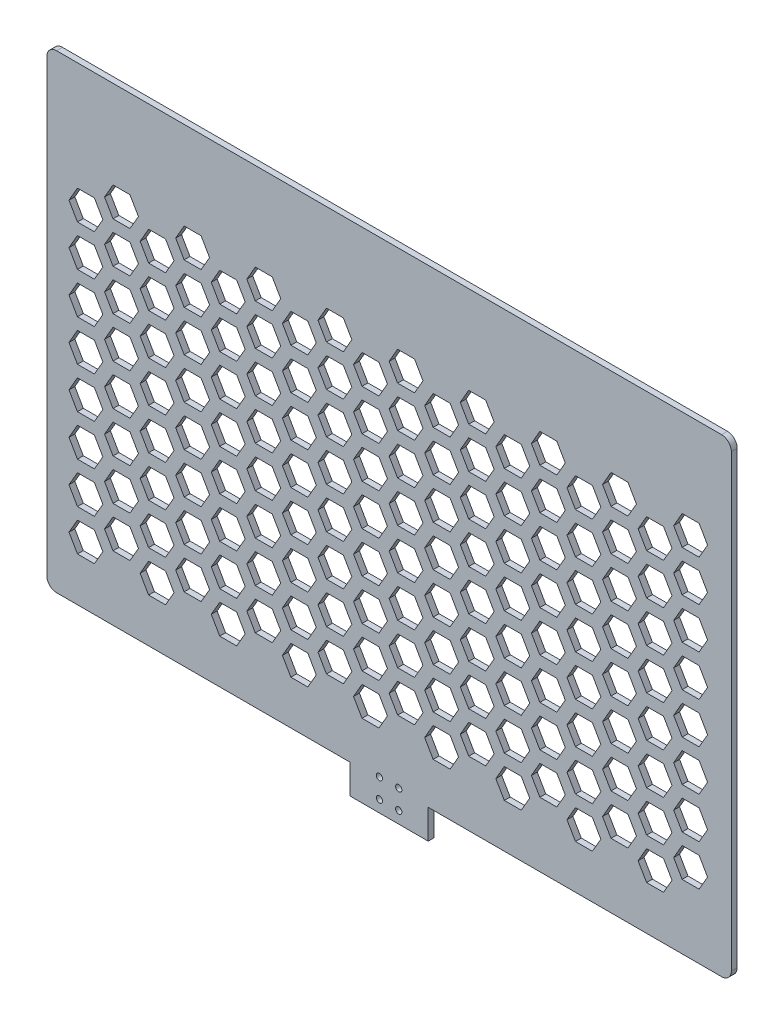
SolidWorks part; units mm, degrees
material "PMMA"
ref_plane "前视基准面" through (0, 0, 0) normal (0, 0, 1) x (1, 0, 0)
ref_plane "上视基准面" through (0, 0, 0) normal (0, 1, 0) x (1, 0, 0)
ref_plane "右视基准面" through (0, 0, 0) normal (1, 0, 0) x (0, 0, -1)
other "Configuration Table"
sketch "草图1" plane through (0, 0, 0) normal (0, 0, 1) x (1, 0, 0)
  line L1 (20, 11) -> (-20, 11)
  line L2 (20, 11) -> (20, -11)
  line L3 (20, -11) -> (-20, -11)
  line L4 (-20, 11) -> (-20, -11)
  line L5 (20, 11) -> (-20, -11) construction
  line L6 (20, -11) -> (-20, 11) construction
  point P0 (0, 0)
  dimension "D1" = 22
  dimension "D2" = 40
extrude "凸台-拉伸1" add sketch "草图1" along normal blind 3
sketch "草图2" plane through (0, 0, 0) normal (0, 0, 1) x (1, 0, 0)
  line L0 (0, 0) -> (0, 50000) construction
  line L1 (-20, -11) -> (20, -11) construction
  line L2 (170, 244) -> (-170, 244)
  line L3 (175, 239) -> (175, 9)
  line L4 (170, 4) -> (-170, 4)
  line L5 (-175, 239) -> (-175, 9)
  line L6 (175, 244) -> (-175, 4) construction
  line L7 (175, 4) -> (-175, 244) construction
  arc A0 (175, 9) -> (170, 4) centre (170, 9) cw
  arc A1 (170, 244) -> (175, 239) centre (170, 239) cw
  arc A2 (-170, 244) -> (-175, 239) centre (-170, 239) ccw
  arc A3 (-170, 4) -> (-175, 9) centre (-170, 9) cw
  point P3 (0, 124)
  dimension "D4" = 5
  dimension "D1" = 240
  dimension "D2" = 350
  dimension "D3" = 15
extrude "凸台-拉伸2" add sketch "草图2" along normal blind 3
sketch "草图4" plane through (0, 0, 0) normal (0, 0, 1) x (1, 0, 0)
  line L1 (4.9497, 4.9497) -> (-4.9497, 4.9497) construction
  line L2 (4.9497, 4.9497) -> (4.9497, -4.9497) construction
  line L3 (4.9497, -4.9497) -> (-4.9497, -4.9497) construction
  line L4 (-4.9497, 4.9497) -> (-4.9497, -4.9497) construction
  line L5 (4.9497, 4.9497) -> (-4.9497, -4.9497) construction
  line L6 (4.9497, -4.9497) -> (-4.9497, 4.9497) construction
  circle A0 centre (-4.9497, 4.9497) radius 1.6
  circle A1 centre (4.9497, 4.9497) radius 1.6
  circle A2 centre (-4.9497, -4.9497) radius 1.6
  circle A3 centre (4.9497, -4.9497) radius 1.6
  point P0 (0, 0)
  dimension "D2" = 3.2
  dimension "D1" = 14
extrude "切除-拉伸1" cut sketch "草图4" along normal through all
sketch "草图5" plane through (0, 0, 3) normal (0, 0, 1) x (1, 0, 0)
  line L0 (-170, 4) -> (-20, 4) construction
  line L1 (-150.6699, 26.5) -> (-146.3397, 34)
  line L2 (-146.3397, 34) -> (-150.6699, 41.5)
  line L3 (-150.6699, 41.5) -> (-159.3301, 41.5)
  line L4 (-159.3301, 41.5) -> (-163.6603, 34)
  line L5 (-163.6603, 34) -> (-159.3301, 26.5)
  line L6 (-159.3301, 26.5) -> (-150.6699, 26.5)
  line L7 (-175, 239) -> (-175, 9) construction
  line L8 (-155, 34) -> (-136.8135, 44.5) construction
  line L9 (-155, 34) -> (-146.3397, 34) construction
  line L10 (-114.2959, 26.5) -> (-109.9657, 34)
  line L11 (-132.4833, 37) -> (-128.1532, 44.5)
  line L12 (-128.1532, 44.5) -> (-132.4833, 52)
  line L13 (-132.4833, 52) -> (-141.1436, 52)
  line L14 (-141.1436, 52) -> (-145.4737, 44.5)
  line L15 (-145.4737, 44.5) -> (-141.1436, 37)
  line L16 (-141.1436, 37) -> (-132.4833, 37)
  line L17 (-109.9657, 34) -> (-114.2959, 41.5)
  line L18 (-114.2959, 41.5) -> (-122.9561, 41.5)
  line L19 (-122.9561, 41.5) -> (-127.2863, 34)
  line L20 (-127.2863, 34) -> (-122.9561, 26.5)
  line L21 (-122.9561, 26.5) -> (-114.2959, 26.5)
  line L22 (-96.1093, 37) -> (-91.7792, 44.5)
  line L23 (-91.7792, 44.5) -> (-96.1093, 52)
  line L24 (-96.1093, 52) -> (-104.7696, 52)
  line L25 (-104.7696, 52) -> (-109.0997, 44.5)
  line L26 (-109.0997, 44.5) -> (-104.7696, 37)
  line L27 (-104.7696, 37) -> (-96.1093, 37)
  line L28 (-77.9219, 26.5) -> (-73.5917, 34)
  line L29 (-73.5917, 34) -> (-77.9219, 41.5)
  line L30 (-77.9219, 41.5) -> (-86.5821, 41.5)
  line L31 (-86.5821, 41.5) -> (-90.9123, 34)
  line L32 (-90.9123, 34) -> (-86.5821, 26.5)
  line L33 (-86.5821, 26.5) -> (-77.9219, 26.5)
  line L34 (-59.7353, 37) -> (-55.4052, 44.5)
  line L35 (-55.4052, 44.5) -> (-59.7353, 52)
  line L36 (-59.7353, 52) -> (-68.3956, 52)
  line L37 (-68.3956, 52) -> (-72.7257, 44.5)
  line L38 (-72.7257, 44.5) -> (-68.3956, 37)
  line L39 (-68.3956, 37) -> (-59.7353, 37)
  line L40 (-41.5479, 26.5) -> (-37.2177, 34)
  line L41 (-37.2177, 34) -> (-41.5479, 41.5)
  line L42 (-41.5479, 41.5) -> (-50.2081, 41.5)
  line L43 (-50.2081, 41.5) -> (-54.5383, 34)
  line L44 (-54.5383, 34) -> (-50.2081, 26.5)
  line L45 (-50.2081, 26.5) -> (-41.5479, 26.5)
  line L46 (-23.3613, 37) -> (-19.0312, 44.5)
  line L47 (-19.0312, 44.5) -> (-23.3613, 52)
  line L48 (-23.3613, 52) -> (-32.0216, 52)
  line L49 (-32.0216, 52) -> (-36.3517, 44.5)
  line L50 (-36.3517, 44.5) -> (-32.0216, 37)
  line L51 (-32.0216, 37) -> (-23.3613, 37)
  line L52 (-5.1739, 26.5) -> (-0.8437, 34)
  line L53 (-0.8437, 34) -> (-5.1739, 41.5)
  line L54 (-5.1739, 41.5) -> (-13.8341, 41.5)
  line L55 (-13.8341, 41.5) -> (-18.1643, 34)
  line L56 (-18.1643, 34) -> (-13.8341, 26.5)
  line L57 (-13.8341, 26.5) -> (-5.1739, 26.5)
  line L58 (13.0127, 37) -> (17.3428, 44.5)
  line L59 (17.3428, 44.5) -> (13.0127, 52)
  line L60 (13.0127, 52) -> (4.3524, 52)
  line L61 (4.3524, 52) -> (0.0223, 44.5)
  line L62 (0.0223, 44.5) -> (4.3524, 37)
  line L63 (4.3524, 37) -> (13.0127, 37)
  line L64 (31.2001, 26.5) -> (35.5303, 34)
  line L65 (35.5303, 34) -> (31.2001, 41.5)
  line L66 (31.2001, 41.5) -> (22.5399, 41.5)
  line L67 (22.5399, 41.5) -> (18.2097, 34)
  line L68 (18.2097, 34) -> (22.5399, 26.5)
  line L69 (22.5399, 26.5) -> (31.2001, 26.5)
  line L70 (49.3867, 37) -> (53.7168, 44.5)
  line L71 (53.7168, 44.5) -> (49.3867, 52)
  line L72 (49.3867, 52) -> (40.7264, 52)
  line L73 (40.7264, 52) -> (36.3963, 44.5)
  line L74 (36.3963, 44.5) -> (40.7264, 37)
  line L75 (40.7264, 37) -> (49.3867, 37)
  line L76 (67.5741, 26.5) -> (71.9043, 34)
  line L77 (71.9043, 34) -> (67.5741, 41.5)
  line L78 (67.5741, 41.5) -> (58.9139, 41.5)
  line L79 (58.9139, 41.5) -> (54.5837, 34)
  line L80 (54.5837, 34) -> (58.9139, 26.5)
  line L81 (58.9139, 26.5) -> (67.5741, 26.5)
  line L82 (85.7607, 37) -> (90.0908, 44.5)
  line L83 (90.0908, 44.5) -> (85.7607, 52)
  line L84 (85.7607, 52) -> (77.1004, 52)
  line L85 (77.1004, 52) -> (72.7703, 44.5)
  line L86 (72.7703, 44.5) -> (77.1004, 37)
  line L87 (77.1004, 37) -> (85.7607, 37)
  line L88 (103.9481, 26.5) -> (108.2783, 34)
  line L89 (108.2783, 34) -> (103.9481, 41.5)
  line L90 (103.9481, 41.5) -> (95.2879, 41.5)
  line L91 (95.2879, 41.5) -> (90.9577, 34)
  line L92 (90.9577, 34) -> (95.2879, 26.5)
  line L93 (95.2879, 26.5) -> (103.9481, 26.5)
  line L94 (122.1347, 37) -> (126.4648, 44.5)
  line L95 (126.4648, 44.5) -> (122.1347, 52)
  line L96 (122.1347, 52) -> (113.4744, 52)
  line L97 (113.4744, 52) -> (109.1443, 44.5)
  line L98 (109.1443, 44.5) -> (113.4744, 37)
  line L99 (113.4744, 37) -> (122.1347, 37)
  line L100 (140.3221, 26.5) -> (144.6523, 34)
  line L101 (144.6523, 34) -> (140.3221, 41.5)
  line L102 (140.3221, 41.5) -> (131.6619, 41.5)
  line L103 (131.6619, 41.5) -> (127.3317, 34)
  line L104 (127.3317, 34) -> (131.6619, 26.5)
  line L105 (131.6619, 26.5) -> (140.3221, 26.5)
  line L106 (158.5087, 37) -> (162.8388, 44.5)
  line L107 (162.8388, 44.5) -> (158.5087, 52)
  line L108 (158.5087, 52) -> (149.8484, 52)
  line L109 (149.8484, 52) -> (145.5183, 44.5)
  line L110 (145.5183, 44.5) -> (149.8484, 37)
  line L111 (149.8484, 37) -> (158.5087, 37)
  line L112 (20, -11) -> (20, 4) construction
  line L113 (-20, -11) -> (20, -11) construction
  line L114 (-150.6699, 47.5) -> (-146.3397, 55)
  line L115 (-146.3397, 55) -> (-150.6699, 62.5)
  line L116 (-150.6699, 62.5) -> (-159.3301, 62.5)
  line L117 (-159.3301, 62.5) -> (-163.6603, 55)
  line L118 (-163.6603, 55) -> (-159.3301, 47.5)
  line L119 (-159.3301, 47.5) -> (-150.6699, 47.5)
  line L120 (-114.2959, 47.5) -> (-109.9657, 55)
  line L121 (-132.4833, 58) -> (-128.1532, 65.5)
  line L122 (-128.1532, 65.5) -> (-132.4833, 73)
  line L123 (-132.4833, 73) -> (-141.1436, 73)
  line L124 (-141.1436, 73) -> (-145.4737, 65.5)
  line L125 (-145.4737, 65.5) -> (-141.1436, 58)
  line L126 (-141.1436, 58) -> (-132.4833, 58)
  line L127 (-109.9657, 55) -> (-114.2959, 62.5)
  line L128 (-114.2959, 62.5) -> (-122.9561, 62.5)
  line L129 (-122.9561, 62.5) -> (-127.2863, 55)
  line L130 (-127.2863, 55) -> (-122.9561, 47.5)
  line L131 (-122.9561, 47.5) -> (-114.2959, 47.5)
  line L132 (-96.1093, 58) -> (-91.7792, 65.5)
  line L133 (-91.7792, 65.5) -> (-96.1093, 73)
  line L134 (-96.1093, 73) -> (-104.7696, 73)
  line L135 (-104.7696, 73) -> (-109.0997, 65.5)
  line L136 (-109.0997, 65.5) -> (-104.7696, 58)
  line L137 (-104.7696, 58) -> (-96.1093, 58)
  line L138 (-77.9219, 47.5) -> (-73.5917, 55)
  line L139 (-73.5917, 55) -> (-77.9219, 62.5)
  line L140 (-77.9219, 62.5) -> (-86.5821, 62.5)
  line L141 (-86.5821, 62.5) -> (-90.9123, 55)
  line L142 (-90.9123, 55) -> (-86.5821, 47.5)
  line L143 (-86.5821, 47.5) -> (-77.9219, 47.5)
  line L144 (-59.7353, 58) -> (-55.4052, 65.5)
  line L145 (-55.4052, 65.5) -> (-59.7353, 73)
  line L146 (-59.7353, 73) -> (-68.3956, 73)
  line L147 (-68.3956, 73) -> (-72.7257, 65.5)
  line L148 (-72.7257, 65.5) -> (-68.3956, 58)
  line L149 (-68.3956, 58) -> (-59.7353, 58)
  line L150 (-41.5479, 47.5) -> (-37.2177, 55)
  line L151 (-37.2177, 55) -> (-41.5479, 62.5)
  line L152 (-41.5479, 62.5) -> (-50.2081, 62.5)
  line L153 (-50.2081, 62.5) -> (-54.5383, 55)
  line L154 (-54.5383, 55) -> (-50.2081, 47.5)
  line L155 (-50.2081, 47.5) -> (-41.5479, 47.5)
  line L156 (-23.3613, 58) -> (-19.0312, 65.5)
  line L157 (-19.0312, 65.5) -> (-23.3613, 73)
  line L158 (-23.3613, 73) -> (-32.0216, 73)
  line L159 (-32.0216, 73) -> (-36.3517, 65.5)
  line L160 (-36.3517, 65.5) -> (-32.0216, 58)
  line L161 (-32.0216, 58) -> (-23.3613, 58)
  line L162 (-5.1739, 47.5) -> (-0.8437, 55)
  line L163 (-0.8437, 55) -> (-5.1739, 62.5)
  line L164 (-5.1739, 62.5) -> (-13.8341, 62.5)
  line L165 (-13.8341, 62.5) -> (-18.1643, 55)
  line L166 (-18.1643, 55) -> (-13.8341, 47.5)
  line L167 (-13.8341, 47.5) -> (-5.1739, 47.5)
  line L168 (13.0127, 58) -> (17.3428, 65.5)
  line L169 (17.3428, 65.5) -> (13.0127, 73)
  line L170 (13.0127, 73) -> (4.3524, 73)
  line L171 (4.3524, 73) -> (0.0223, 65.5)
  line L172 (0.0223, 65.5) -> (4.3524, 58)
  line L173 (4.3524, 58) -> (13.0127, 58)
  line L174 (31.2001, 47.5) -> (35.5303, 55)
  line L175 (35.5303, 55) -> (31.2001, 62.5)
  line L176 (31.2001, 62.5) -> (22.5399, 62.5)
  line L177 (22.5399, 62.5) -> (18.2097, 55)
  line L178 (18.2097, 55) -> (22.5399, 47.5)
  line L179 (22.5399, 47.5) -> (31.2001, 47.5)
  line L180 (49.3867, 58) -> (53.7168, 65.5)
  line L181 (53.7168, 65.5) -> (49.3867, 73)
  line L182 (49.3867, 73) -> (40.7264, 73)
  line L183 (40.7264, 73) -> (36.3963, 65.5)
  line L184 (36.3963, 65.5) -> (40.7264, 58)
  line L185 (40.7264, 58) -> (49.3867, 58)
  line L186 (67.5741, 47.5) -> (71.9043, 55)
  line L187 (71.9043, 55) -> (67.5741, 62.5)
  line L188 (67.5741, 62.5) -> (58.9139, 62.5)
  line L189 (58.9139, 62.5) -> (54.5837, 55)
  line L190 (54.5837, 55) -> (58.9139, 47.5)
  line L191 (58.9139, 47.5) -> (67.5741, 47.5)
  line L192 (85.7607, 58) -> (90.0908, 65.5)
  line L193 (90.0908, 65.5) -> (85.7607, 73)
  line L194 (85.7607, 73) -> (77.1004, 73)
  line L195 (77.1004, 73) -> (72.7703, 65.5)
  line L196 (72.7703, 65.5) -> (77.1004, 58)
  line L197 (77.1004, 58) -> (85.7607, 58)
  line L198 (103.9481, 47.5) -> (108.2783, 55)
  line L199 (108.2783, 55) -> (103.9481, 62.5)
  line L200 (103.9481, 62.5) -> (95.2879, 62.5)
  line L201 (95.2879, 62.5) -> (90.9577, 55)
  line L202 (90.9577, 55) -> (95.2879, 47.5)
  line L203 (95.2879, 47.5) -> (103.9481, 47.5)
  line L204 (122.1347, 58) -> (126.4648, 65.5)
  line L205 (126.4648, 65.5) -> (122.1347, 73)
  line L206 (122.1347, 73) -> (113.4744, 73)
  line L207 (113.4744, 73) -> (109.1443, 65.5)
  line L208 (109.1443, 65.5) -> (113.4744, 58)
  line L209 (113.4744, 58) -> (122.1347, 58)
  line L210 (140.3221, 47.5) -> (144.6523, 55)
  line L211 (144.6523, 55) -> (140.3221, 62.5)
  line L212 (140.3221, 62.5) -> (131.6619, 62.5)
  line L213 (131.6619, 62.5) -> (127.3317, 55)
  line L214 (127.3317, 55) -> (131.6619, 47.5)
  line L215 (131.6619, 47.5) -> (140.3221, 47.5)
  line L216 (158.5087, 58) -> (162.8388, 65.5)
  line L217 (162.8388, 65.5) -> (158.5087, 73)
  line L218 (158.5087, 73) -> (149.8484, 73)
  line L219 (149.8484, 73) -> (145.5183, 65.5)
  line L220 (145.5183, 65.5) -> (149.8484, 58)
  line L221 (149.8484, 58) -> (158.5087, 58)
  line L222 (-155, 55) -> (-136.8135, 65.5) construction
  line L223 (-155, 55) -> (-146.3397, 55) construction
  line L224 (-150.6699, 68.5) -> (-146.3397, 76)
  line L225 (-146.3397, 76) -> (-150.6699, 83.5)
  line L226 (-150.6699, 83.5) -> (-159.3301, 83.5)
  line L227 (-159.3301, 83.5) -> (-163.6603, 76)
  line L228 (-163.6603, 76) -> (-159.3301, 68.5)
  line L229 (-159.3301, 68.5) -> (-150.6699, 68.5)
  line L230 (-114.2959, 68.5) -> (-109.9657, 76)
  line L231 (-132.4833, 79) -> (-128.1532, 86.5)
  line L232 (-128.1532, 86.5) -> (-132.4833, 94)
  line L233 (-132.4833, 94) -> (-141.1436, 94)
  line L234 (-141.1436, 94) -> (-145.4737, 86.5)
  line L235 (-145.4737, 86.5) -> (-141.1436, 79)
  line L236 (-141.1436, 79) -> (-132.4833, 79)
  line L237 (-109.9657, 76) -> (-114.2959, 83.5)
  line L238 (-114.2959, 83.5) -> (-122.9561, 83.5)
  line L239 (-122.9561, 83.5) -> (-127.2863, 76)
  line L240 (-127.2863, 76) -> (-122.9561, 68.5)
  line L241 (-122.9561, 68.5) -> (-114.2959, 68.5)
  line L242 (-96.1093, 79) -> (-91.7792, 86.5)
  line L243 (-91.7792, 86.5) -> (-96.1093, 94)
  line L244 (-96.1093, 94) -> (-104.7696, 94)
  line L245 (-104.7696, 94) -> (-109.0997, 86.5)
  line L246 (-109.0997, 86.5) -> (-104.7696, 79)
  line L247 (-104.7696, 79) -> (-96.1093, 79)
  line L248 (-77.9219, 68.5) -> (-73.5917, 76)
  line L249 (-73.5917, 76) -> (-77.9219, 83.5)
  line L250 (-77.9219, 83.5) -> (-86.5821, 83.5)
  line L251 (-86.5821, 83.5) -> (-90.9123, 76)
  line L252 (-90.9123, 76) -> (-86.5821, 68.5)
  line L253 (-86.5821, 68.5) -> (-77.9219, 68.5)
  line L254 (-59.7353, 79) -> (-55.4052, 86.5)
  line L255 (-55.4052, 86.5) -> (-59.7353, 94)
  line L256 (-59.7353, 94) -> (-68.3956, 94)
  line L257 (-68.3956, 94) -> (-72.7257, 86.5)
  line L258 (-72.7257, 86.5) -> (-68.3956, 79)
  line L259 (-68.3956, 79) -> (-59.7353, 79)
  line L260 (-41.5479, 68.5) -> (-37.2177, 76)
  line L261 (-37.2177, 76) -> (-41.5479, 83.5)
  line L262 (-41.5479, 83.5) -> (-50.2081, 83.5)
  line L263 (-50.2081, 83.5) -> (-54.5383, 76)
  line L264 (-54.5383, 76) -> (-50.2081, 68.5)
  line L265 (-50.2081, 68.5) -> (-41.5479, 68.5)
  line L266 (-23.3613, 79) -> (-19.0312, 86.5)
  line L267 (-19.0312, 86.5) -> (-23.3613, 94)
  line L268 (-23.3613, 94) -> (-32.0216, 94)
  line L269 (-32.0216, 94) -> (-36.3517, 86.5)
  line L270 (-36.3517, 86.5) -> (-32.0216, 79)
  line L271 (-32.0216, 79) -> (-23.3613, 79)
  line L272 (-5.1739, 68.5) -> (-0.8437, 76)
  line L273 (-0.8437, 76) -> (-5.1739, 83.5)
  line L274 (-5.1739, 83.5) -> (-13.8341, 83.5)
  line L275 (-13.8341, 83.5) -> (-18.1643, 76)
  line L276 (-18.1643, 76) -> (-13.8341, 68.5)
  line L277 (-13.8341, 68.5) -> (-5.1739, 68.5)
  line L278 (13.0127, 79) -> (17.3428, 86.5)
  line L279 (17.3428, 86.5) -> (13.0127, 94)
  line L280 (13.0127, 94) -> (4.3524, 94)
  line L281 (4.3524, 94) -> (0.0223, 86.5)
  line L282 (0.0223, 86.5) -> (4.3524, 79)
  line L283 (4.3524, 79) -> (13.0127, 79)
  line L284 (31.2001, 68.5) -> (35.5303, 76)
  line L285 (35.5303, 76) -> (31.2001, 83.5)
  line L286 (31.2001, 83.5) -> (22.5399, 83.5)
  line L287 (22.5399, 83.5) -> (18.2097, 76)
  line L288 (18.2097, 76) -> (22.5399, 68.5)
  line L289 (22.5399, 68.5) -> (31.2001, 68.5)
  line L290 (49.3867, 79) -> (53.7168, 86.5)
  line L291 (53.7168, 86.5) -> (49.3867, 94)
  line L292 (49.3867, 94) -> (40.7264, 94)
  line L293 (40.7264, 94) -> (36.3963, 86.5)
  line L294 (36.3963, 86.5) -> (40.7264, 79)
  line L295 (40.7264, 79) -> (49.3867, 79)
  line L296 (67.5741, 68.5) -> (71.9043, 76)
  line L297 (71.9043, 76) -> (67.5741, 83.5)
  line L298 (67.5741, 83.5) -> (58.9139, 83.5)
  line L299 (58.9139, 83.5) -> (54.5837, 76)
  line L300 (54.5837, 76) -> (58.9139, 68.5)
  line L301 (58.9139, 68.5) -> (67.5741, 68.5)
  line L302 (85.7607, 79) -> (90.0908, 86.5)
  line L303 (90.0908, 86.5) -> (85.7607, 94)
  line L304 (85.7607, 94) -> (77.1004, 94)
  line L305 (77.1004, 94) -> (72.7703, 86.5)
  line L306 (72.7703, 86.5) -> (77.1004, 79)
  line L307 (77.1004, 79) -> (85.7607, 79)
  line L308 (103.9481, 68.5) -> (108.2783, 76)
  line L309 (108.2783, 76) -> (103.9481, 83.5)
  line L310 (103.9481, 83.5) -> (95.2879, 83.5)
  line L311 (95.2879, 83.5) -> (90.9577, 76)
  line L312 (90.9577, 76) -> (95.2879, 68.5)
  line L313 (95.2879, 68.5) -> (103.9481, 68.5)
  line L314 (122.1347, 79) -> (126.4648, 86.5)
  line L315 (126.4648, 86.5) -> (122.1347, 94)
  line L316 (122.1347, 94) -> (113.4744, 94)
  line L317 (113.4744, 94) -> (109.1443, 86.5)
  line L318 (109.1443, 86.5) -> (113.4744, 79)
  line L319 (113.4744, 79) -> (122.1347, 79)
  line L320 (140.3221, 68.5) -> (144.6523, 76)
  line L321 (144.6523, 76) -> (140.3221, 83.5)
  line L322 (140.3221, 83.5) -> (131.6619, 83.5)
  line L323 (131.6619, 83.5) -> (127.3317, 76)
  line L324 (127.3317, 76) -> (131.6619, 68.5)
  line L325 (131.6619, 68.5) -> (140.3221, 68.5)
  line L326 (158.5087, 79) -> (162.8388, 86.5)
  line L327 (162.8388, 86.5) -> (158.5087, 94)
  line L328 (158.5087, 94) -> (149.8484, 94)
  line L329 (149.8484, 94) -> (145.5183, 86.5)
  line L330 (145.5183, 86.5) -> (149.8484, 79)
  line L331 (149.8484, 79) -> (158.5087, 79)
  line L332 (-155, 76) -> (-136.8135, 86.5) construction
  line L333 (-155, 76) -> (-146.3397, 76) construction
  line L334 (-150.6699, 89.5) -> (-146.3397, 97)
  line L335 (-146.3397, 97) -> (-150.6699, 104.5)
  line L336 (-150.6699, 104.5) -> (-159.3301, 104.5)
  line L337 (-159.3301, 104.5) -> (-163.6603, 97)
  line L338 (-163.6603, 97) -> (-159.3301, 89.5)
  line L339 (-159.3301, 89.5) -> (-150.6699, 89.5)
  line L340 (-114.2959, 89.5) -> (-109.9657, 97)
  line L341 (-132.4833, 100) -> (-128.1532, 107.5)
  line L342 (-128.1532, 107.5) -> (-132.4833, 115)
  line L343 (-132.4833, 115) -> (-141.1436, 115)
  line L344 (-141.1436, 115) -> (-145.4737, 107.5)
  line L345 (-145.4737, 107.5) -> (-141.1436, 100)
  line L346 (-141.1436, 100) -> (-132.4833, 100)
  line L347 (-109.9657, 97) -> (-114.2959, 104.5)
  line L348 (-114.2959, 104.5) -> (-122.9561, 104.5)
  line L349 (-122.9561, 104.5) -> (-127.2863, 97)
  line L350 (-127.2863, 97) -> (-122.9561, 89.5)
  line L351 (-122.9561, 89.5) -> (-114.2959, 89.5)
  line L352 (-96.1093, 100) -> (-91.7792, 107.5)
  line L353 (-91.7792, 107.5) -> (-96.1093, 115)
  line L354 (-96.1093, 115) -> (-104.7696, 115)
  line L355 (-104.7696, 115) -> (-109.0997, 107.5)
  line L356 (-109.0997, 107.5) -> (-104.7696, 100)
  line L357 (-104.7696, 100) -> (-96.1093, 100)
  line L358 (-77.9219, 89.5) -> (-73.5917, 97)
  line L359 (-73.5917, 97) -> (-77.9219, 104.5)
  line L360 (-77.9219, 104.5) -> (-86.5821, 104.5)
  line L361 (-86.5821, 104.5) -> (-90.9123, 97)
  line L362 (-90.9123, 97) -> (-86.5821, 89.5)
  line L363 (-86.5821, 89.5) -> (-77.9219, 89.5)
  line L364 (-59.7353, 100) -> (-55.4052, 107.5)
  line L365 (-55.4052, 107.5) -> (-59.7353, 115)
  line L366 (-59.7353, 115) -> (-68.3956, 115)
  line L367 (-68.3956, 115) -> (-72.7257, 107.5)
  line L368 (-72.7257, 107.5) -> (-68.3956, 100)
  line L369 (-68.3956, 100) -> (-59.7353, 100)
  line L370 (-41.5479, 89.5) -> (-37.2177, 97)
  line L371 (-37.2177, 97) -> (-41.5479, 104.5)
  line L372 (-41.5479, 104.5) -> (-50.2081, 104.5)
  line L373 (-50.2081, 104.5) -> (-54.5383, 97)
  line L374 (-54.5383, 97) -> (-50.2081, 89.5)
  line L375 (-50.2081, 89.5) -> (-41.5479, 89.5)
  line L376 (-23.3613, 100) -> (-19.0312, 107.5)
  line L377 (-19.0312, 107.5) -> (-23.3613, 115)
  line L378 (-23.3613, 115) -> (-32.0216, 115)
  line L379 (-32.0216, 115) -> (-36.3517, 107.5)
  line L380 (-36.3517, 107.5) -> (-32.0216, 100)
  line L381 (-32.0216, 100) -> (-23.3613, 100)
  line L382 (-5.1739, 89.5) -> (-0.8437, 97)
  line L383 (-0.8437, 97) -> (-5.1739, 104.5)
  line L384 (-5.1739, 104.5) -> (-13.8341, 104.5)
  line L385 (-13.8341, 104.5) -> (-18.1643, 97)
  line L386 (-18.1643, 97) -> (-13.8341, 89.5)
  line L387 (-13.8341, 89.5) -> (-5.1739, 89.5)
  line L388 (13.0127, 100) -> (17.3428, 107.5)
  line L389 (17.3428, 107.5) -> (13.0127, 115)
  line L390 (13.0127, 115) -> (4.3524, 115)
  line L391 (4.3524, 115) -> (0.0223, 107.5)
  line L392 (0.0223, 107.5) -> (4.3524, 100)
  line L393 (4.3524, 100) -> (13.0127, 100)
  line L394 (31.2001, 89.5) -> (35.5303, 97)
  line L395 (35.5303, 97) -> (31.2001, 104.5)
  line L396 (31.2001, 104.5) -> (22.5399, 104.5)
  line L397 (22.5399, 104.5) -> (18.2097, 97)
  line L398 (18.2097, 97) -> (22.5399, 89.5)
  line L399 (22.5399, 89.5) -> (31.2001, 89.5)
  line L400 (49.3867, 100) -> (53.7168, 107.5)
  line L401 (53.7168, 107.5) -> (49.3867, 115)
  line L402 (49.3867, 115) -> (40.7264, 115)
  line L403 (40.7264, 115) -> (36.3963, 107.5)
  line L404 (36.3963, 107.5) -> (40.7264, 100)
  line L405 (40.7264, 100) -> (49.3867, 100)
  line L406 (67.5741, 89.5) -> (71.9043, 97)
  line L407 (71.9043, 97) -> (67.5741, 104.5)
  line L408 (67.5741, 104.5) -> (58.9139, 104.5)
  line L409 (58.9139, 104.5) -> (54.5837, 97)
  line L410 (54.5837, 97) -> (58.9139, 89.5)
  line L411 (58.9139, 89.5) -> (67.5741, 89.5)
  line L412 (85.7607, 100) -> (90.0908, 107.5)
  line L413 (90.0908, 107.5) -> (85.7607, 115)
  line L414 (85.7607, 115) -> (77.1004, 115)
  line L415 (77.1004, 115) -> (72.7703, 107.5)
  line L416 (72.7703, 107.5) -> (77.1004, 100)
  line L417 (77.1004, 100) -> (85.7607, 100)
  line L418 (103.9481, 89.5) -> (108.2783, 97)
  line L419 (108.2783, 97) -> (103.9481, 104.5)
  line L420 (103.9481, 104.5) -> (95.2879, 104.5)
  line L421 (95.2879, 104.5) -> (90.9577, 97)
  line L422 (90.9577, 97) -> (95.2879, 89.5)
  line L423 (95.2879, 89.5) -> (103.9481, 89.5)
  line L424 (122.1347, 100) -> (126.4648, 107.5)
  line L425 (126.4648, 107.5) -> (122.1347, 115)
  line L426 (122.1347, 115) -> (113.4744, 115)
  line L427 (113.4744, 115) -> (109.1443, 107.5)
  line L428 (109.1443, 107.5) -> (113.4744, 100)
  line L429 (113.4744, 100) -> (122.1347, 100)
  line L430 (140.3221, 89.5) -> (144.6523, 97)
  line L431 (144.6523, 97) -> (140.3221, 104.5)
  line L432 (140.3221, 104.5) -> (131.6619, 104.5)
  line L433 (131.6619, 104.5) -> (127.3317, 97)
  line L434 (127.3317, 97) -> (131.6619, 89.5)
  line L435 (131.6619, 89.5) -> (140.3221, 89.5)
  line L436 (158.5087, 100) -> (162.8388, 107.5)
  line L437 (162.8388, 107.5) -> (158.5087, 115)
  line L438 (158.5087, 115) -> (149.8484, 115)
  line L439 (149.8484, 115) -> (145.5183, 107.5)
  line L440 (145.5183, 107.5) -> (149.8484, 100)
  line L441 (149.8484, 100) -> (158.5087, 100)
  line L442 (-155, 97) -> (-136.8135, 107.5) construction
  line L443 (-155, 97) -> (-146.3397, 97) construction
  line L444 (-150.6699, 110.5) -> (-146.3397, 118)
  line L445 (-146.3397, 118) -> (-150.6699, 125.5)
  line L446 (-150.6699, 125.5) -> (-159.3301, 125.5)
  line L447 (-159.3301, 125.5) -> (-163.6603, 118)
  line L448 (-163.6603, 118) -> (-159.3301, 110.5)
  line L449 (-159.3301, 110.5) -> (-150.6699, 110.5)
  line L450 (-114.2959, 110.5) -> (-109.9657, 118)
  line L451 (-132.4833, 121) -> (-128.1532, 128.5)
  line L452 (-128.1532, 128.5) -> (-132.4833, 136)
  line L453 (-132.4833, 136) -> (-141.1436, 136)
  line L454 (-141.1436, 136) -> (-145.4737, 128.5)
  line L455 (-145.4737, 128.5) -> (-141.1436, 121)
  line L456 (-141.1436, 121) -> (-132.4833, 121)
  line L457 (-109.9657, 118) -> (-114.2959, 125.5)
  line L458 (-114.2959, 125.5) -> (-122.9561, 125.5)
  line L459 (-122.9561, 125.5) -> (-127.2863, 118)
  line L460 (-127.2863, 118) -> (-122.9561, 110.5)
  line L461 (-122.9561, 110.5) -> (-114.2959, 110.5)
  line L462 (-96.1093, 121) -> (-91.7792, 128.5)
  line L463 (-91.7792, 128.5) -> (-96.1093, 136)
  line L464 (-96.1093, 136) -> (-104.7696, 136)
  line L465 (-104.7696, 136) -> (-109.0997, 128.5)
  line L466 (-109.0997, 128.5) -> (-104.7696, 121)
  line L467 (-104.7696, 121) -> (-96.1093, 121)
  line L468 (-77.9219, 110.5) -> (-73.5917, 118)
  line L469 (-73.5917, 118) -> (-77.9219, 125.5)
  line L470 (-77.9219, 125.5) -> (-86.5821, 125.5)
  line L471 (-86.5821, 125.5) -> (-90.9123, 118)
  line L472 (-90.9123, 118) -> (-86.5821, 110.5)
  line L473 (-86.5821, 110.5) -> (-77.9219, 110.5)
  line L474 (-59.7353, 121) -> (-55.4052, 128.5)
  line L475 (-55.4052, 128.5) -> (-59.7353, 136)
  line L476 (-59.7353, 136) -> (-68.3956, 136)
  line L477 (-68.3956, 136) -> (-72.7257, 128.5)
  line L478 (-72.7257, 128.5) -> (-68.3956, 121)
  line L479 (-68.3956, 121) -> (-59.7353, 121)
  line L480 (-41.5479, 110.5) -> (-37.2177, 118)
  line L481 (-37.2177, 118) -> (-41.5479, 125.5)
  line L482 (-41.5479, 125.5) -> (-50.2081, 125.5)
  line L483 (-50.2081, 125.5) -> (-54.5383, 118)
  line L484 (-54.5383, 118) -> (-50.2081, 110.5)
  line L485 (-50.2081, 110.5) -> (-41.5479, 110.5)
  line L486 (-23.3613, 121) -> (-19.0312, 128.5)
  line L487 (-19.0312, 128.5) -> (-23.3613, 136)
  line L488 (-23.3613, 136) -> (-32.0216, 136)
  line L489 (-32.0216, 136) -> (-36.3517, 128.5)
  line L490 (-36.3517, 128.5) -> (-32.0216, 121)
  line L491 (-32.0216, 121) -> (-23.3613, 121)
  line L492 (-5.1739, 110.5) -> (-0.8437, 118)
  line L493 (-0.8437, 118) -> (-5.1739, 125.5)
  line L494 (-5.1739, 125.5) -> (-13.8341, 125.5)
  line L495 (-13.8341, 125.5) -> (-18.1643, 118)
  line L496 (-18.1643, 118) -> (-13.8341, 110.5)
  line L497 (-13.8341, 110.5) -> (-5.1739, 110.5)
  line L498 (13.0127, 121) -> (17.3428, 128.5)
  line L499 (17.3428, 128.5) -> (13.0127, 136)
  line L500 (13.0127, 136) -> (4.3524, 136)
  line L501 (4.3524, 136) -> (0.0223, 128.5)
  line L502 (0.0223, 128.5) -> (4.3524, 121)
  line L503 (4.3524, 121) -> (13.0127, 121)
  line L504 (31.2001, 110.5) -> (35.5303, 118)
  line L505 (35.5303, 118) -> (31.2001, 125.5)
  line L506 (31.2001, 125.5) -> (22.5399, 125.5)
  line L507 (22.5399, 125.5) -> (18.2097, 118)
  line L508 (18.2097, 118) -> (22.5399, 110.5)
  line L509 (22.5399, 110.5) -> (31.2001, 110.5)
  line L510 (49.3867, 121) -> (53.7168, 128.5)
  line L511 (53.7168, 128.5) -> (49.3867, 136)
  line L512 (49.3867, 136) -> (40.7264, 136)
  line L513 (40.7264, 136) -> (36.3963, 128.5)
  line L514 (36.3963, 128.5) -> (40.7264, 121)
  line L515 (40.7264, 121) -> (49.3867, 121)
  line L516 (67.5741, 110.5) -> (71.9043, 118)
  line L517 (71.9043, 118) -> (67.5741, 125.5)
  line L518 (67.5741, 125.5) -> (58.9139, 125.5)
  line L519 (58.9139, 125.5) -> (54.5837, 118)
  line L520 (54.5837, 118) -> (58.9139, 110.5)
  line L521 (58.9139, 110.5) -> (67.5741, 110.5)
  line L522 (85.7607, 121) -> (90.0908, 128.5)
  line L523 (90.0908, 128.5) -> (85.7607, 136)
  line L524 (85.7607, 136) -> (77.1004, 136)
  line L525 (77.1004, 136) -> (72.7703, 128.5)
  line L526 (72.7703, 128.5) -> (77.1004, 121)
  line L527 (77.1004, 121) -> (85.7607, 121)
  line L528 (103.9481, 110.5) -> (108.2783, 118)
  line L529 (108.2783, 118) -> (103.9481, 125.5)
  line L530 (103.9481, 125.5) -> (95.2879, 125.5)
  line L531 (95.2879, 125.5) -> (90.9577, 118)
  line L532 (90.9577, 118) -> (95.2879, 110.5)
  line L533 (95.2879, 110.5) -> (103.9481, 110.5)
  line L534 (122.1347, 121) -> (126.4648, 128.5)
  line L535 (126.4648, 128.5) -> (122.1347, 136)
  line L536 (122.1347, 136) -> (113.4744, 136)
  line L537 (113.4744, 136) -> (109.1443, 128.5)
  line L538 (109.1443, 128.5) -> (113.4744, 121)
  line L539 (113.4744, 121) -> (122.1347, 121)
  line L540 (140.3221, 110.5) -> (144.6523, 118)
  line L541 (144.6523, 118) -> (140.3221, 125.5)
  line L542 (140.3221, 125.5) -> (131.6619, 125.5)
  line L543 (131.6619, 125.5) -> (127.3317, 118)
  line L544 (127.3317, 118) -> (131.6619, 110.5)
  line L545 (131.6619, 110.5) -> (140.3221, 110.5)
  line L546 (158.5087, 121) -> (162.8388, 128.5)
  line L547 (162.8388, 128.5) -> (158.5087, 136)
  line L548 (158.5087, 136) -> (149.8484, 136)
  line L549 (149.8484, 136) -> (145.5183, 128.5)
  line L550 (145.5183, 128.5) -> (149.8484, 121)
  line L551 (149.8484, 121) -> (158.5087, 121)
  line L552 (-155, 118) -> (-136.8135, 128.5) construction
  line L553 (-155, 118) -> (-146.3397, 118) construction
  line L554 (-150.6699, 131.5) -> (-146.3397, 139)
  line L555 (-146.3397, 139) -> (-150.6699, 146.5)
  line L556 (-150.6699, 146.5) -> (-159.3301, 146.5)
  line L557 (-159.3301, 146.5) -> (-163.6603, 139)
  line L558 (-163.6603, 139) -> (-159.3301, 131.5)
  line L559 (-159.3301, 131.5) -> (-150.6699, 131.5)
  line L560 (-114.2959, 131.5) -> (-109.9657, 139)
  line L561 (-132.4833, 142) -> (-128.1532, 149.5)
  line L562 (-128.1532, 149.5) -> (-132.4833, 157)
  line L563 (-132.4833, 157) -> (-141.1436, 157)
  line L564 (-141.1436, 157) -> (-145.4737, 149.5)
  line L565 (-145.4737, 149.5) -> (-141.1436, 142)
  line L566 (-141.1436, 142) -> (-132.4833, 142)
  line L567 (-109.9657, 139) -> (-114.2959, 146.5)
  line L568 (-114.2959, 146.5) -> (-122.9561, 146.5)
  line L569 (-122.9561, 146.5) -> (-127.2863, 139)
  line L570 (-127.2863, 139) -> (-122.9561, 131.5)
  line L571 (-122.9561, 131.5) -> (-114.2959, 131.5)
  line L572 (-96.1093, 142) -> (-91.7792, 149.5)
  line L573 (-91.7792, 149.5) -> (-96.1093, 157)
  line L574 (-96.1093, 157) -> (-104.7696, 157)
  line L575 (-104.7696, 157) -> (-109.0997, 149.5)
  line L576 (-109.0997, 149.5) -> (-104.7696, 142)
  line L577 (-104.7696, 142) -> (-96.1093, 142)
  line L578 (-77.9219, 131.5) -> (-73.5917, 139)
  line L579 (-73.5917, 139) -> (-77.9219, 146.5)
  line L580 (-77.9219, 146.5) -> (-86.5821, 146.5)
  line L581 (-86.5821, 146.5) -> (-90.9123, 139)
  line L582 (-90.9123, 139) -> (-86.5821, 131.5)
  line L583 (-86.5821, 131.5) -> (-77.9219, 131.5)
  line L584 (-59.7353, 142) -> (-55.4052, 149.5)
  line L585 (-55.4052, 149.5) -> (-59.7353, 157)
  line L586 (-59.7353, 157) -> (-68.3956, 157)
  line L587 (-68.3956, 157) -> (-72.7257, 149.5)
  line L588 (-72.7257, 149.5) -> (-68.3956, 142)
  line L589 (-68.3956, 142) -> (-59.7353, 142)
  line L590 (-41.5479, 131.5) -> (-37.2177, 139)
  line L591 (-37.2177, 139) -> (-41.5479, 146.5)
  line L592 (-41.5479, 146.5) -> (-50.2081, 146.5)
  line L593 (-50.2081, 146.5) -> (-54.5383, 139)
  line L594 (-54.5383, 139) -> (-50.2081, 131.5)
  line L595 (-50.2081, 131.5) -> (-41.5479, 131.5)
  line L596 (-23.3613, 142) -> (-19.0312, 149.5)
  line L597 (-19.0312, 149.5) -> (-23.3613, 157)
  line L598 (-23.3613, 157) -> (-32.0216, 157)
  line L599 (-32.0216, 157) -> (-36.3517, 149.5)
  line L600 (-36.3517, 149.5) -> (-32.0216, 142)
  line L601 (-32.0216, 142) -> (-23.3613, 142)
  line L602 (-5.1739, 131.5) -> (-0.8437, 139)
  line L603 (-0.8437, 139) -> (-5.1739, 146.5)
  line L604 (-5.1739, 146.5) -> (-13.8341, 146.5)
  line L605 (-13.8341, 146.5) -> (-18.1643, 139)
  line L606 (-18.1643, 139) -> (-13.8341, 131.5)
  line L607 (-13.8341, 131.5) -> (-5.1739, 131.5)
  line L608 (13.0127, 142) -> (17.3428, 149.5)
  line L609 (17.3428, 149.5) -> (13.0127, 157)
  line L610 (13.0127, 157) -> (4.3524, 157)
  line L611 (4.3524, 157) -> (0.0223, 149.5)
  line L612 (0.0223, 149.5) -> (4.3524, 142)
  line L613 (4.3524, 142) -> (13.0127, 142)
  line L614 (31.2001, 131.5) -> (35.5303, 139)
  line L615 (35.5303, 139) -> (31.2001, 146.5)
  line L616 (31.2001, 146.5) -> (22.5399, 146.5)
  line L617 (22.5399, 146.5) -> (18.2097, 139)
  line L618 (18.2097, 139) -> (22.5399, 131.5)
  line L619 (22.5399, 131.5) -> (31.2001, 131.5)
  line L620 (49.3867, 142) -> (53.7168, 149.5)
  line L621 (53.7168, 149.5) -> (49.3867, 157)
  line L622 (49.3867, 157) -> (40.7264, 157)
  line L623 (40.7264, 157) -> (36.3963, 149.5)
  line L624 (36.3963, 149.5) -> (40.7264, 142)
  line L625 (40.7264, 142) -> (49.3867, 142)
  line L626 (67.5741, 131.5) -> (71.9043, 139)
  line L627 (71.9043, 139) -> (67.5741, 146.5)
  line L628 (67.5741, 146.5) -> (58.9139, 146.5)
  line L629 (58.9139, 146.5) -> (54.5837, 139)
  line L630 (54.5837, 139) -> (58.9139, 131.5)
  line L631 (58.9139, 131.5) -> (67.5741, 131.5)
  line L632 (85.7607, 142) -> (90.0908, 149.5)
  line L633 (90.0908, 149.5) -> (85.7607, 157)
  line L634 (85.7607, 157) -> (77.1004, 157)
  line L635 (77.1004, 157) -> (72.7703, 149.5)
  line L636 (72.7703, 149.5) -> (77.1004, 142)
  line L637 (77.1004, 142) -> (85.7607, 142)
  line L638 (103.9481, 131.5) -> (108.2783, 139)
  line L639 (108.2783, 139) -> (103.9481, 146.5)
  line L640 (103.9481, 146.5) -> (95.2879, 146.5)
  line L641 (95.2879, 146.5) -> (90.9577, 139)
  line L642 (90.9577, 139) -> (95.2879, 131.5)
  line L643 (95.2879, 131.5) -> (103.9481, 131.5)
  line L644 (122.1347, 142) -> (126.4648, 149.5)
  line L645 (126.4648, 149.5) -> (122.1347, 157)
  line L646 (122.1347, 157) -> (113.4744, 157)
  line L647 (113.4744, 157) -> (109.1443, 149.5)
  line L648 (109.1443, 149.5) -> (113.4744, 142)
  line L649 (113.4744, 142) -> (122.1347, 142)
  line L650 (140.3221, 131.5) -> (144.6523, 139)
  line L651 (144.6523, 139) -> (140.3221, 146.5)
  line L652 (140.3221, 146.5) -> (131.6619, 146.5)
  line L653 (131.6619, 146.5) -> (127.3317, 139)
  line L654 (127.3317, 139) -> (131.6619, 131.5)
  line L655 (131.6619, 131.5) -> (140.3221, 131.5)
  line L656 (158.5087, 142) -> (162.8388, 149.5)
  line L657 (162.8388, 149.5) -> (158.5087, 157)
  line L658 (158.5087, 157) -> (149.8484, 157)
  line L659 (149.8484, 157) -> (145.5183, 149.5)
  line L660 (145.5183, 149.5) -> (149.8484, 142)
  line L661 (149.8484, 142) -> (158.5087, 142)
  line L662 (-155, 139) -> (-136.8135, 149.5) construction
  line L663 (-155, 139) -> (-146.3397, 139) construction
  line L664 (-150.6699, 152.5) -> (-146.3397, 160)
  line L665 (-146.3397, 160) -> (-150.6699, 167.5)
  line L666 (-150.6699, 167.5) -> (-159.3301, 167.5)
  line L667 (-159.3301, 167.5) -> (-163.6603, 160)
  line L668 (-163.6603, 160) -> (-159.3301, 152.5)
  line L669 (-159.3301, 152.5) -> (-150.6699, 152.5)
  line L670 (-114.2959, 152.5) -> (-109.9657, 160)
  line L671 (-132.4833, 163) -> (-128.1532, 170.5)
  line L672 (-128.1532, 170.5) -> (-132.4833, 178)
  line L673 (-132.4833, 178) -> (-141.1436, 178)
  line L674 (-141.1436, 178) -> (-145.4737, 170.5)
  line L675 (-145.4737, 170.5) -> (-141.1436, 163)
  line L676 (-141.1436, 163) -> (-132.4833, 163)
  line L677 (-109.9657, 160) -> (-114.2959, 167.5)
  line L678 (-114.2959, 167.5) -> (-122.9561, 167.5)
  line L679 (-122.9561, 167.5) -> (-127.2863, 160)
  line L680 (-127.2863, 160) -> (-122.9561, 152.5)
  line L681 (-122.9561, 152.5) -> (-114.2959, 152.5)
  line L682 (-96.1093, 163) -> (-91.7792, 170.5)
  line L683 (-91.7792, 170.5) -> (-96.1093, 178)
  line L684 (-96.1093, 178) -> (-104.7696, 178)
  line L685 (-104.7696, 178) -> (-109.0997, 170.5)
  line L686 (-109.0997, 170.5) -> (-104.7696, 163)
  line L687 (-104.7696, 163) -> (-96.1093, 163)
  line L688 (-77.9219, 152.5) -> (-73.5917, 160)
  line L689 (-73.5917, 160) -> (-77.9219, 167.5)
  line L690 (-77.9219, 167.5) -> (-86.5821, 167.5)
  line L691 (-86.5821, 167.5) -> (-90.9123, 160)
  line L692 (-90.9123, 160) -> (-86.5821, 152.5)
  line L693 (-86.5821, 152.5) -> (-77.9219, 152.5)
  line L694 (-59.7353, 163) -> (-55.4052, 170.5)
  line L695 (-55.4052, 170.5) -> (-59.7353, 178)
  line L696 (-59.7353, 178) -> (-68.3956, 178)
  line L697 (-68.3956, 178) -> (-72.7257, 170.5)
  line L698 (-72.7257, 170.5) -> (-68.3956, 163)
  line L699 (-68.3956, 163) -> (-59.7353, 163)
  line L700 (-41.5479, 152.5) -> (-37.2177, 160)
  line L701 (-37.2177, 160) -> (-41.5479, 167.5)
  line L702 (-41.5479, 167.5) -> (-50.2081, 167.5)
  line L703 (-50.2081, 167.5) -> (-54.5383, 160)
  line L704 (-54.5383, 160) -> (-50.2081, 152.5)
  line L705 (-50.2081, 152.5) -> (-41.5479, 152.5)
  line L706 (-23.3613, 163) -> (-19.0312, 170.5)
  line L707 (-19.0312, 170.5) -> (-23.3613, 178)
  line L708 (-23.3613, 178) -> (-32.0216, 178)
  line L709 (-32.0216, 178) -> (-36.3517, 170.5)
  line L710 (-36.3517, 170.5) -> (-32.0216, 163)
  line L711 (-32.0216, 163) -> (-23.3613, 163)
  line L712 (-5.1739, 152.5) -> (-0.8437, 160)
  line L713 (-0.8437, 160) -> (-5.1739, 167.5)
  line L714 (-5.1739, 167.5) -> (-13.8341, 167.5)
  line L715 (-13.8341, 167.5) -> (-18.1643, 160)
  line L716 (-18.1643, 160) -> (-13.8341, 152.5)
  line L717 (-13.8341, 152.5) -> (-5.1739, 152.5)
  line L718 (13.0127, 163) -> (17.3428, 170.5)
  line L719 (17.3428, 170.5) -> (13.0127, 178)
  line L720 (13.0127, 178) -> (4.3524, 178)
  line L721 (4.3524, 178) -> (0.0223, 170.5)
  line L722 (0.0223, 170.5) -> (4.3524, 163)
  line L723 (4.3524, 163) -> (13.0127, 163)
  line L724 (31.2001, 152.5) -> (35.5303, 160)
  line L725 (35.5303, 160) -> (31.2001, 167.5)
  line L726 (31.2001, 167.5) -> (22.5399, 167.5)
  line L727 (22.5399, 167.5) -> (18.2097, 160)
  line L728 (18.2097, 160) -> (22.5399, 152.5)
  line L729 (22.5399, 152.5) -> (31.2001, 152.5)
  line L730 (49.3867, 163) -> (53.7168, 170.5)
  line L731 (53.7168, 170.5) -> (49.3867, 178)
  line L732 (49.3867, 178) -> (40.7264, 178)
  line L733 (40.7264, 178) -> (36.3963, 170.5)
  line L734 (36.3963, 170.5) -> (40.7264, 163)
  line L735 (40.7264, 163) -> (49.3867, 163)
  line L736 (67.5741, 152.5) -> (71.9043, 160)
  line L737 (71.9043, 160) -> (67.5741, 167.5)
  line L738 (67.5741, 167.5) -> (58.9139, 167.5)
  line L739 (58.9139, 167.5) -> (54.5837, 160)
  line L740 (54.5837, 160) -> (58.9139, 152.5)
  line L741 (58.9139, 152.5) -> (67.5741, 152.5)
  line L742 (85.7607, 163) -> (90.0908, 170.5)
  line L743 (90.0908, 170.5) -> (85.7607, 178)
  line L744 (85.7607, 178) -> (77.1004, 178)
  line L745 (77.1004, 178) -> (72.7703, 170.5)
  line L746 (72.7703, 170.5) -> (77.1004, 163)
  line L747 (77.1004, 163) -> (85.7607, 163)
  line L748 (103.9481, 152.5) -> (108.2783, 160)
  line L749 (108.2783, 160) -> (103.9481, 167.5)
  line L750 (103.9481, 167.5) -> (95.2879, 167.5)
  line L751 (95.2879, 167.5) -> (90.9577, 160)
  line L752 (90.9577, 160) -> (95.2879, 152.5)
  line L753 (95.2879, 152.5) -> (103.9481, 152.5)
  line L754 (122.1347, 163) -> (126.4648, 170.5)
  line L755 (126.4648, 170.5) -> (122.1347, 178)
  line L756 (122.1347, 178) -> (113.4744, 178)
  line L757 (113.4744, 178) -> (109.1443, 170.5)
  line L758 (109.1443, 170.5) -> (113.4744, 163)
  line L759 (113.4744, 163) -> (122.1347, 163)
  line L760 (140.3221, 152.5) -> (144.6523, 160)
  line L761 (144.6523, 160) -> (140.3221, 167.5)
  line L762 (140.3221, 167.5) -> (131.6619, 167.5)
  line L763 (131.6619, 167.5) -> (127.3317, 160)
  line L764 (127.3317, 160) -> (131.6619, 152.5)
  line L765 (131.6619, 152.5) -> (140.3221, 152.5)
  line L766 (158.5087, 163) -> (162.8388, 170.5)
  line L767 (162.8388, 170.5) -> (158.5087, 178)
  line L768 (158.5087, 178) -> (149.8484, 178)
  line L769 (149.8484, 178) -> (145.5183, 170.5)
  line L770 (145.5183, 170.5) -> (149.8484, 163)
  line L771 (149.8484, 163) -> (158.5087, 163)
  line L772 (-155, 160) -> (-136.8135, 170.5) construction
  line L773 (-155, 160) -> (-146.3397, 160) construction
  line L774 (-150.6699, 173.5) -> (-146.3397, 181)
  line L775 (-146.3397, 181) -> (-150.6699, 188.5)
  line L776 (-150.6699, 188.5) -> (-159.3301, 188.5)
  line L777 (-159.3301, 188.5) -> (-163.6603, 181)
  line L778 (-163.6603, 181) -> (-159.3301, 173.5)
  line L779 (-159.3301, 173.5) -> (-150.6699, 173.5)
  line L780 (-114.2959, 173.5) -> (-109.9657, 181)
  line L781 (-132.4833, 184) -> (-128.1532, 191.5)
  line L782 (-128.1532, 191.5) -> (-132.4833, 199)
  line L783 (-132.4833, 199) -> (-141.1436, 199)
  line L784 (-141.1436, 199) -> (-145.4737, 191.5)
  line L785 (-145.4737, 191.5) -> (-141.1436, 184)
  line L786 (-141.1436, 184) -> (-132.4833, 184)
  line L787 (-109.9657, 181) -> (-114.2959, 188.5)
  line L788 (-114.2959, 188.5) -> (-122.9561, 188.5)
  line L789 (-122.9561, 188.5) -> (-127.2863, 181)
  line L790 (-127.2863, 181) -> (-122.9561, 173.5)
  line L791 (-122.9561, 173.5) -> (-114.2959, 173.5)
  line L792 (-96.1093, 184) -> (-91.7792, 191.5)
  line L793 (-91.7792, 191.5) -> (-96.1093, 199)
  line L794 (-96.1093, 199) -> (-104.7696, 199)
  line L795 (-104.7696, 199) -> (-109.0997, 191.5)
  line L796 (-109.0997, 191.5) -> (-104.7696, 184)
  line L797 (-104.7696, 184) -> (-96.1093, 184)
  line L798 (-77.9219, 173.5) -> (-73.5917, 181)
  line L799 (-73.5917, 181) -> (-77.9219, 188.5)
  line L800 (-77.9219, 188.5) -> (-86.5821, 188.5)
  line L801 (-86.5821, 188.5) -> (-90.9123, 181)
  line L802 (-90.9123, 181) -> (-86.5821, 173.5)
  line L803 (-86.5821, 173.5) -> (-77.9219, 173.5)
  line L804 (-59.7353, 184) -> (-55.4052, 191.5)
  line L805 (-55.4052, 191.5) -> (-59.7353, 199)
  line L806 (-59.7353, 199) -> (-68.3956, 199)
  line L807 (-68.3956, 199) -> (-72.7257, 191.5)
  line L808 (-72.7257, 191.5) -> (-68.3956, 184)
  line L809 (-68.3956, 184) -> (-59.7353, 184)
  line L810 (-41.5479, 173.5) -> (-37.2177, 181)
  line L811 (-37.2177, 181) -> (-41.5479, 188.5)
  line L812 (-41.5479, 188.5) -> (-50.2081, 188.5)
  line L813 (-50.2081, 188.5) -> (-54.5383, 181)
  line L814 (-54.5383, 181) -> (-50.2081, 173.5)
  line L815 (-50.2081, 173.5) -> (-41.5479, 173.5)
  line L816 (-23.3613, 184) -> (-19.0312, 191.5)
  line L817 (-19.0312, 191.5) -> (-23.3613, 199)
  line L818 (-23.3613, 199) -> (-32.0216, 199)
  line L819 (-32.0216, 199) -> (-36.3517, 191.5)
  line L820 (-36.3517, 191.5) -> (-32.0216, 184)
  line L821 (-32.0216, 184) -> (-23.3613, 184)
  line L822 (-5.1739, 173.5) -> (-0.8437, 181)
  line L823 (-0.8437, 181) -> (-5.1739, 188.5)
  line L824 (-5.1739, 188.5) -> (-13.8341, 188.5)
  line L825 (-13.8341, 188.5) -> (-18.1643, 181)
  line L826 (-18.1643, 181) -> (-13.8341, 173.5)
  line L827 (-13.8341, 173.5) -> (-5.1739, 173.5)
  line L828 (13.0127, 184) -> (17.3428, 191.5)
  line L829 (17.3428, 191.5) -> (13.0127, 199)
  line L830 (13.0127, 199) -> (4.3524, 199)
  line L831 (4.3524, 199) -> (0.0223, 191.5)
  line L832 (0.0223, 191.5) -> (4.3524, 184)
  line L833 (4.3524, 184) -> (13.0127, 184)
  line L834 (31.2001, 173.5) -> (35.5303, 181)
  line L835 (35.5303, 181) -> (31.2001, 188.5)
  line L836 (31.2001, 188.5) -> (22.5399, 188.5)
  line L837 (22.5399, 188.5) -> (18.2097, 181)
  line L838 (18.2097, 181) -> (22.5399, 173.5)
  line L839 (22.5399, 173.5) -> (31.2001, 173.5)
  line L840 (49.3867, 184) -> (53.7168, 191.5)
  line L841 (53.7168, 191.5) -> (49.3867, 199)
  line L842 (49.3867, 199) -> (40.7264, 199)
  line L843 (40.7264, 199) -> (36.3963, 191.5)
  line L844 (36.3963, 191.5) -> (40.7264, 184)
  line L845 (40.7264, 184) -> (49.3867, 184)
  line L846 (67.5741, 173.5) -> (71.9043, 181)
  line L847 (71.9043, 181) -> (67.5741, 188.5)
  line L848 (67.5741, 188.5) -> (58.9139, 188.5)
  line L849 (58.9139, 188.5) -> (54.5837, 181)
  line L850 (54.5837, 181) -> (58.9139, 173.5)
  line L851 (58.9139, 173.5) -> (67.5741, 173.5)
  line L852 (85.7607, 184) -> (90.0908, 191.5)
  line L853 (90.0908, 191.5) -> (85.7607, 199)
  line L854 (85.7607, 199) -> (77.1004, 199)
  line L855 (77.1004, 199) -> (72.7703, 191.5)
  line L856 (72.7703, 191.5) -> (77.1004, 184)
  line L857 (77.1004, 184) -> (85.7607, 184)
  line L858 (103.9481, 173.5) -> (108.2783, 181)
  line L859 (108.2783, 181) -> (103.9481, 188.5)
  line L860 (103.9481, 188.5) -> (95.2879, 188.5)
  line L861 (95.2879, 188.5) -> (90.9577, 181)
  line L862 (90.9577, 181) -> (95.2879, 173.5)
  line L863 (95.2879, 173.5) -> (103.9481, 173.5)
  line L864 (122.1347, 184) -> (126.4648, 191.5)
  line L865 (126.4648, 191.5) -> (122.1347, 199)
  line L866 (122.1347, 199) -> (113.4744, 199)
  line L867 (113.4744, 199) -> (109.1443, 191.5)
  line L868 (109.1443, 191.5) -> (113.4744, 184)
  line L869 (113.4744, 184) -> (122.1347, 184)
  line L870 (140.3221, 173.5) -> (144.6523, 181)
  line L871 (144.6523, 181) -> (140.3221, 188.5)
  line L872 (140.3221, 188.5) -> (131.6619, 188.5)
  line L873 (131.6619, 188.5) -> (127.3317, 181)
  line L874 (127.3317, 181) -> (131.6619, 173.5)
  line L875 (131.6619, 173.5) -> (140.3221, 173.5)
  line L876 (158.5087, 184) -> (162.8388, 191.5)
  line L877 (162.8388, 191.5) -> (158.5087, 199)
  line L878 (158.5087, 199) -> (149.8484, 199)
  line L879 (149.8484, 199) -> (145.5183, 191.5)
  line L880 (145.5183, 191.5) -> (149.8484, 184)
  line L881 (149.8484, 184) -> (158.5087, 184)
  line L882 (-155, 181) -> (-136.8135, 191.5) construction
  line L883 (-155, 181) -> (-146.3397, 181) construction
  circle A0 centre (-155, 34) radius 7.5 construction
  circle A1 centre (-136.8135, 44.5) radius 7.5 construction
  circle A2 centre (-155, 55) radius 7.5 construction
  circle A3 centre (-136.8135, 65.5) radius 7.5 construction
  circle A4 centre (-155, 76) radius 7.5 construction
  circle A5 centre (-136.8135, 86.5) radius 7.5 construction
  circle A6 centre (-155, 97) radius 7.5 construction
  circle A7 centre (-136.8135, 107.5) radius 7.5 construction
  circle A8 centre (-155, 118) radius 7.5 construction
  circle A9 centre (-136.8135, 128.5) radius 7.5 construction
  circle A10 centre (-155, 139) radius 7.5 construction
  circle A11 centre (-136.8135, 149.5) radius 7.5 construction
  circle A12 centre (-155, 160) radius 7.5 construction
  circle A13 centre (-136.8135, 170.5) radius 7.5 construction
  circle A14 centre (-155, 181) radius 7.5 construction
  circle A15 centre (-136.8135, 191.5) radius 7.5 construction
  point P16 (-136.8135, 37)
  dimension "D4" = 6
  dimension "D1" = 15
  dimension "D2" = 30
  dimension "D3" = 20
  dimension "D5" = 15
  dimension "D6" = 30
  dimension "D7" = 9
  dimension "D8" = 6.0008
  dimension "D9" = 8
  dimension "D10" = 6
extrude "切除-拉伸2" cut sketch "草图5" against normal blind 10
